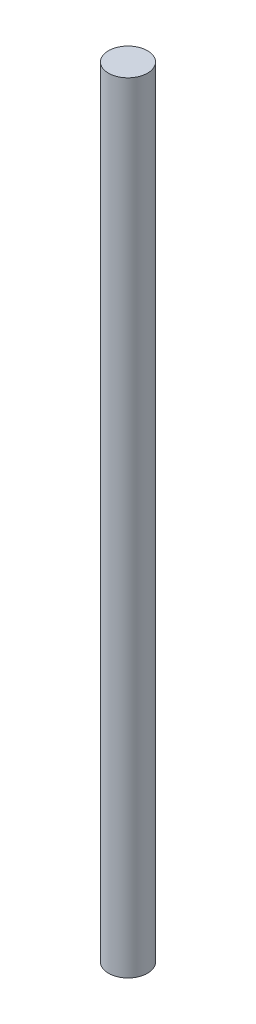
SolidWorks part; units mm, degrees
ref_plane "Front Plane" through (0, 0, 0) normal (0, 0, 1) x (1, 0, 0)
ref_plane "Top Plane" through (0, 0, 0) normal (0, 1, 0) x (1, 0, 0)
ref_plane "Right Plane" through (0, 0, 0) normal (1, 0, 0) x (0, 0, -1)
sketch "Sketch1" plane through (0, 0, 0) normal (0, 1, 0) x (1, 0, 0)
  circle A0 centre (0, 0) radius 1.4732
  dimension "D1" = 2.9464
extrude "Boss-Extrude1" add sketch "Sketch1" along normal blind 58.9026
